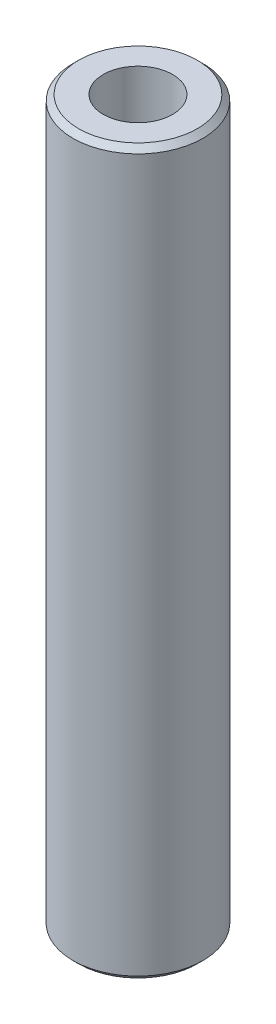
SolidWorks part; units mm, degrees
ref_plane "Front Plane" through (0, 0, 0) normal (0, 0, 1) x (1, 0, 0)
ref_plane "Top Plane" through (0, 0, 0) normal (0, 1, 0) x (1, 0, 0)
ref_plane "Right Plane" through (0, 0, 0) normal (1, 0, 0) x (0, 0, -1)
sketch "Sketch1" plane through (0, 0, 0) normal (0, 1, 0) x (1, 0, 0)
  circle A0 centre (0, 0) radius 42.5
  dimension "SHAFT_OD" = 85
extrude "Boss-Extrude1" add sketch "Sketch1" along normal blind 473.3873
sketch "Sketch2" plane through (0, 0, 0) normal (0, 1, 0) x (1, 0, 0)
  circle A0 centre (0, 0) radius 22.6834
  dimension "BORE_D" = 45.3667
extrude "Cut-Extrude1" cut sketch "Sketch2" along normal through all
chamfer "Chamfer1" distance 3.6587 angle 45 2 edges at (0, 473.3873, 42.5) (0, 0, 42.5)
